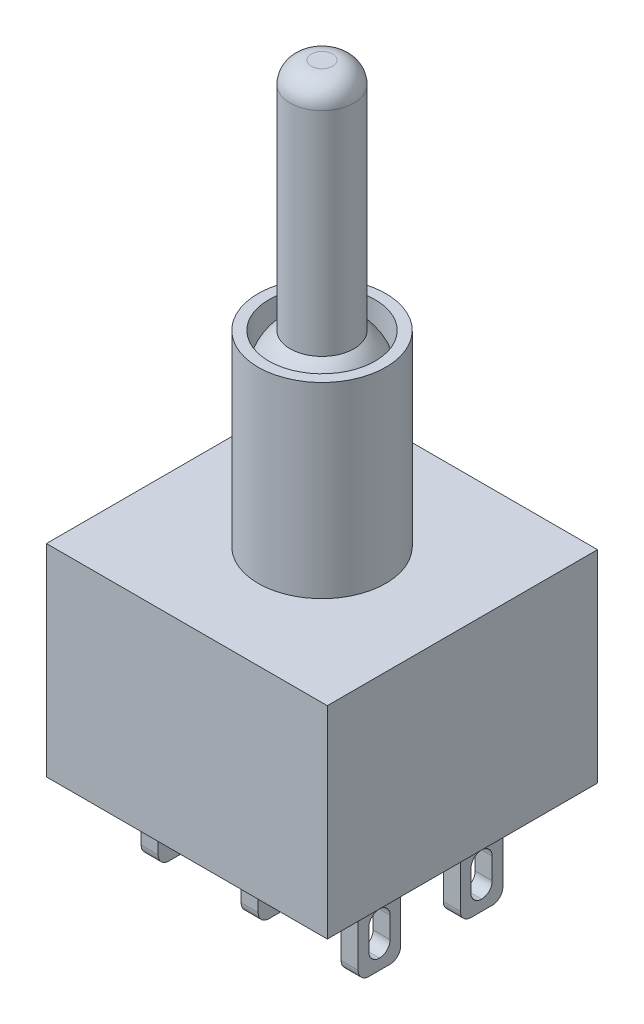
SolidWorks part; units mm, degrees
ref_plane "Спереди" through (0, 0, 0) normal (0, 0, 1) x (1, 0, 0)
ref_plane "Сверху" through (0, 0, 0) normal (0, 1, 0) x (1, 0, 0)
ref_plane "Справа" through (0, 0, 0) normal (1, 0, 0) x (0, 0, -1)
sketch "Sketch1" plane through (0, 0, 0) normal (0, 1, 0) x (1, 0, 0)
  line L1 (6.6, -6.35) -> (-6.6, -6.35)
  line L2 (6.6, -6.35) -> (6.6, 6.35)
  line L3 (6.6, 6.35) -> (-6.6, 6.35)
  line L4 (-6.6, -6.35) -> (-6.6, 6.35)
  line L5 (6.6, -6.35) -> (-6.6, 6.35) construction
  line L6 (6.6, 6.35) -> (-6.6, -6.35) construction
  point P0 (0, 0)
  dimension "D1" = 13.2
  dimension "D2" = 12.7
extrude "Boss-Extrude1" add sketch "Sketch1" along normal blind 9.5
sketch "Sketch2" plane through (0, 9.5, 0) normal (0, 1, 0) x (1, 0, 0)
  line L0 (-6.6, 6.35) -> (6.6, -6.35) construction
  circle A0 centre (0, 0) radius 3
  dimension "D1" = 6
extrude "Boss-Extrude2" add sketch "Sketch2" along normal blind 8.8
sketch "Sketch4" plane through (0, 18.3, 0) normal (0, 1, 0) x (1, 0, 0)
  circle A0 centre (0, 0) radius 2.5
  dimension "D1" = 5
extrude "Cut-Extrude1" cut sketch "Sketch4" against normal blind 2
sketch "Sketch5" plane through (0, 16.3, 0) normal (0, 1, 0) x (1, 0, 0)
  circle A0 centre (0, 0) radius 1.5
  dimension "D1" = 3
extrude "Boss-Extrude3" add sketch "Sketch5" along normal blind 13
sketch "Sketch3" plane through (0, 16.3, 0) normal (0, 1, 0) x (1, 0, 0)
  line L0 (0, -3) -> (0, 3) construction
  line L1 (0, -2.5) -> (0, 2.5)
  circle A0 centre (0, 0) radius 3 construction
  arc A1 (0, -2.5) -> (0, 2.5) centre (0, 0) cw
  point P7 (0, 0)
  dimension "D1" = 5
revolve "Revolve2" add sketch "Sketch3" angle 180 about L0
fillet "Fillet1" radius 1 1 edges at (0, 29.3, 1.5)
sketch "Sketch6" plane through (0, 0, 0) normal (0, -1, 0) x (1, 0, 0)
  line L0 (-4.7, 6.35) -> (-4.7, -6.35) construction
  line L1 (-6.6, 6.35) -> (6.6, 6.35) construction
  line L2 (6.6, -6.35) -> (-6.6, -6.35) construction
  line L3 (0, 6.35) -> (0, -6.35) construction
  line L4 (4.7, 6.35) -> (4.7, -6.35) construction
  line L6 (-6.6, 2.4) -> (6.6, 2.4) construction
  line L7 (-4.3, 1.4) -> (-5.1, 1.4)
  line L8 (-4.3, 1.4) -> (-4.3, 3.4)
  line L9 (-4.3, 3.4) -> (-5.1, 3.4)
  line L10 (-5.1, 1.4) -> (-5.1, 3.4)
  line L11 (-4.3, 1.4) -> (-5.1, 3.4) construction
  line L12 (-4.3, 3.4) -> (-5.1, 1.4) construction
  line L13 (-6.6, -6.35) -> (-6.6, 6.35) construction
  line L14 (6.6, 6.35) -> (6.6, -6.35) construction
  line L15 (-6.6, -2.4) -> (6.6, -2.4) construction
  line L16 (-6.6, 0) -> (6.6, 0) construction
  line L17 (-4.3, -3.4) -> (-5.1, -3.4)
  line L18 (-4.3, -3.4) -> (-4.3, -1.4)
  line L19 (-4.3, -1.4) -> (-5.1, -1.4)
  line L20 (-5.1, -3.4) -> (-5.1, -1.4)
  line L21 (-4.3, -3.4) -> (-5.1, -1.4) construction
  line L22 (-4.3, -1.4) -> (-5.1, -3.4) construction
  line L23 (0.4, -3.4) -> (-0.4, -3.4)
  line L24 (0.4, -3.4) -> (0.4, -1.4)
  line L25 (0.4, -1.4) -> (-0.4, -1.4)
  line L26 (-0.4, -3.4) -> (-0.4, -1.4)
  line L27 (0.4, -3.4) -> (-0.4, -1.4) construction
  line L28 (0.4, -1.4) -> (-0.4, -3.4) construction
  line L29 (0.4, 1.4) -> (-0.4, 1.4)
  line L30 (0.4, 1.4) -> (0.4, 3.4)
  line L31 (0.4, 3.4) -> (-0.4, 3.4)
  line L32 (-0.4, 1.4) -> (-0.4, 3.4)
  line L33 (0.4, 1.4) -> (-0.4, 3.4) construction
  line L34 (0.4, 3.4) -> (-0.4, 1.4) construction
  line L35 (5.1, 1.4) -> (4.3, 1.4)
  line L36 (5.1, 1.4) -> (5.1, 3.4)
  line L37 (5.1, 3.4) -> (4.3, 3.4)
  line L38 (4.3, 1.4) -> (4.3, 3.4)
  line L39 (5.1, 1.4) -> (4.3, 3.4) construction
  line L40 (5.1, 3.4) -> (4.3, 1.4) construction
  line L41 (5.1, -3.4) -> (4.3, -3.4)
  line L42 (5.1, -3.4) -> (5.1, -1.4)
  line L43 (5.1, -1.4) -> (4.3, -1.4)
  line L44 (4.3, -3.4) -> (4.3, -1.4)
  line L45 (5.1, -3.4) -> (4.3, -1.4) construction
  line L46 (5.1, -1.4) -> (4.3, -3.4) construction
  point P10 (0, 0)
  point P11 (-4.7, 2.4)
  point P27 (-4.7, -2.4)
  point P32 (0, -2.4)
  point P37 (0, 2.4)
  point P42 (4.7, 2.4)
  point P47 (4.7, -2.4)
  dimension "D1" = 4.7
  dimension "D2" = 4.7
  dimension "D3" = 2
  dimension "D4" = 0.8
  dimension "D5" = 4.8
  dimension "D6" = 2.4
extrude "Boss-Extrude4" add sketch "Sketch6" along normal blind 4
sketch "Sketch7" plane through (-5.1, 0, 0) normal (-1, 0, 0) x (0, 0, 1)
  line L0 (-2.4, -4) -> (-2.4, 0) construction
  line L1 (-1.4, -4) -> (-3.4, -4) construction
  line L2 (-1.4, 0) -> (-3.4, 0) construction
  line L3 (2.4, -4) -> (2.4, 0) construction
  line L6 (3.4, -4) -> (1.4, -4) construction
  line L7 (3.4, 0) -> (1.4, 0) construction
  line L8 (-3.4, -2.5) -> (3.4, -2.5) construction
  line L9 (-1.9, -3.5) -> (-2.9, -3.5)
  line L10 (-1.9, -3.5) -> (-1.9, -1.5)
  line L11 (-1.9, -1.5) -> (-2.9, -1.5)
  line L12 (-2.9, -3.5) -> (-2.9, -1.5)
  line L13 (-1.9, -3.5) -> (-2.9, -1.5) construction
  line L14 (-1.9, -1.5) -> (-2.9, -3.5) construction
  line L15 (2.9, -3.5) -> (1.9, -3.5)
  line L16 (2.9, -3.5) -> (2.9, -1.5)
  line L17 (2.9, -1.5) -> (1.9, -1.5)
  line L18 (1.9, -3.5) -> (1.9, -1.5)
  line L19 (2.9, -3.5) -> (1.9, -1.5) construction
  line L20 (2.9, -1.5) -> (1.9, -3.5) construction
  line L21 (-3.4, -4) -> (-3.4, 0) construction
  line L22 (3.4, -4) -> (3.4, 0) construction
  point P12 (-2.4, -2.5)
  point P17 (2.4, -2.5)
  point P28 (0, 0)
  dimension "D1" = 0.5
  dimension "D2" = 2
  dimension "D3" = 1
extrude "Cut-Extrude2" cut sketch "Sketch7" against normal through all
fillet "Fillet2" radius 0.5 36 edges at (4.7, -3.5, 2.9) (4.7, -3.5, 1.9) (4.7, -3.5, -1.9) (4.7, -3.5, -2.9) (4.7, -1.5, -1.9) (4.7, -1.5, 2.9) (4.7, -1.5, 1.9) (4.7, -1.5, -2.9) (0, -1.5, 1.9) (0, -1.5, 2.9) (0, -3.5, 2.9) (0, -3.5, 1.9) (0, -3.5, -1.9) (0, -3.5, -2.9) (0, -1.5, -2.9) (0, -1.5, -1.9) (-4.7, -3.5, 2.9) (-4.7, -1.5, 2.9) (-4.7, -3.5, 1.9) (-4.7, -1.5, 1.9) (-4.7, -1.5, -1.9) (-4.7, -1.5, -2.9) (-4.7, -3.5, -1.9) (-4.7, -3.5, -2.9) (0, -4, -1.4) (0, -4, -3.4) (4.7, -4, -1.4) (4.7, -4, -3.4) (4.7, -4, 1.4) (4.7, -4, 3.4) (0, -4, 3.4) (0, -4, 1.4) (-4.7, -4, 3.4) (-4.7, -4, 1.4) (-4.7, -4, -1.4) (-4.7, -4, -3.4)
